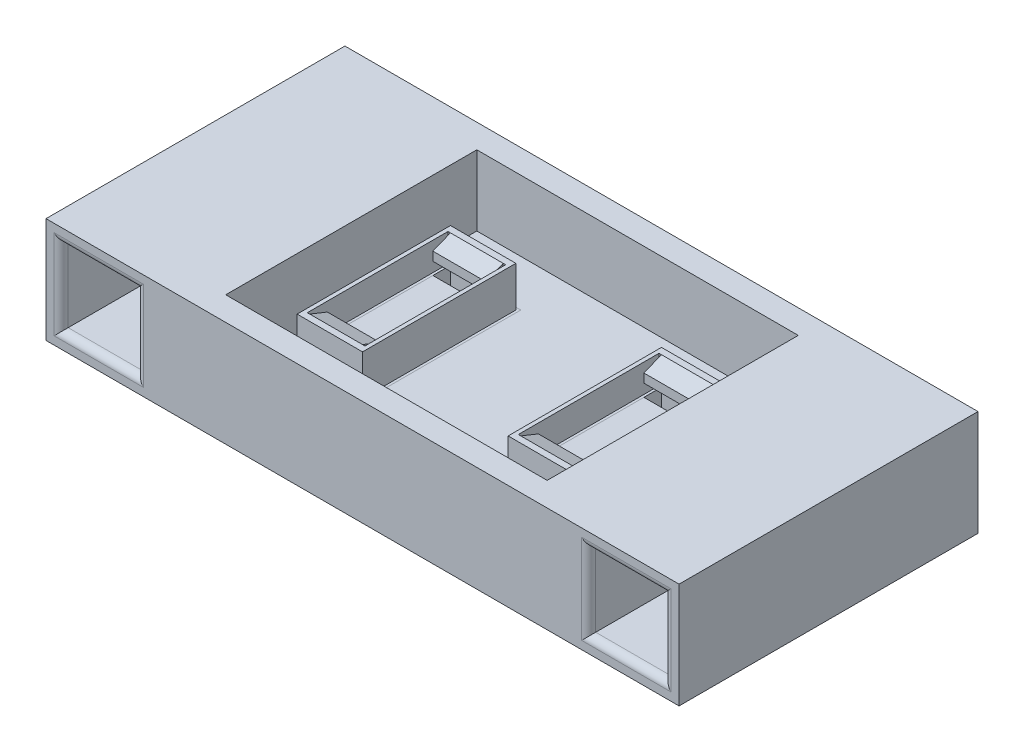
SolidWorks part; units mm, degrees
material "Custom Plastic"
ref_plane "Front Plane" through (0, 0, 0) normal (0, 0, 1) x (1, 0, 0)
ref_plane "Top Plane" through (0, 0, 0) normal (0, 1, 0) x (1, 0, 0)
ref_plane "Right Plane" through (0, 0, 0) normal (1, 0, 0) x (0, 0, -1)
sketch "Sketch1" plane through (0, 0, 0) normal (0, 1, 0) x (1, 0, 0)
  line L1 (-82.9493, 33.6982) -> (97.0507, 33.6982)
  line L2 (-82.9493, 33.6982) -> (-82.9493, -51.3018)
  line L3 (-82.9493, -51.3018) -> (97.0507, -51.3018)
  line L4 (97.0507, 33.6982) -> (97.0507, -51.3018)
  dimension "D1" = 180
  dimension "D2" = 85
extrude "Boss-Extrude1" add sketch "Sketch1" along normal blind 30
sketch "Sketch2" plane through (0, 0, 51.3018) normal (0, 0, 1) x (1, 0, 0)
  line L0 (-82.9493, 0) -> (97.0507, 0) construction
  line L1 (-77.9493, 25) -> (-57.9493, 25)
  line L2 (-77.9493, 25) -> (-77.9493, 5)
  line L3 (-77.9493, 5) -> (-57.9493, 5)
  line L4 (-57.9493, 25) -> (-57.9493, 5)
  line L5 (-77.9493, 25) -> (-57.9493, 5) construction
  line L6 (-77.9493, 5) -> (-57.9493, 25) construction
  line L7 (72.0507, 25) -> (92.0507, 25)
  line L8 (72.0507, 25) -> (72.0507, 5)
  line L9 (72.0507, 5) -> (92.0507, 5)
  line L10 (92.0507, 25) -> (92.0507, 5)
  line L11 (72.0507, 25) -> (92.0507, 5) construction
  line L12 (72.0507, 5) -> (92.0507, 25) construction
  line L13 (-82.9493, 30) -> (-82.9493, 0) construction
  line L14 (97.0507, 30) -> (97.0507, 0) construction
  point P0 (-67.9493, 15)
  point P5 (82.0507, 15)
  dimension "D1" = 15
  dimension "D2" = 20
  dimension "D3" = 20
  dimension "D4" = 15
  dimension "D5" = 20
  dimension "D6" = 20
  dimension "D7" = 15
  dimension "D8" = 15
extrude "Cut-Extrude1" cut sketch "Sketch2" against normal blind 75
sketch "Sketch3" plane through (0, 30, 0) normal (0, 1, 0) x (1, 0, 0)
  line L0 (-82.9493, 33.6982) -> (-82.9493, -51.3018) construction
  line L1 (-37.9493, 26.1982) -> (52.0507, 26.1982)
  line L2 (-37.9493, 26.1982) -> (-37.9493, -43.8018)
  line L3 (-37.9493, -43.8018) -> (52.0507, -43.8018)
  line L4 (52.0507, 26.1982) -> (52.0507, -43.8018)
  line L5 (-37.9493, 26.1982) -> (52.0507, -43.8018) construction
  line L6 (-37.9493, -43.8018) -> (52.0507, 26.1982) construction
  line L8 (-82.9493, -51.3018) -> (97.0507, -51.3018) construction
  line L9 (97.0507, -51.3018) -> (97.0507, 33.6982) construction
  point P0 (7.0507, -8.8018)
  dimension "D1" = 90
  dimension "D2" = 70
  dimension "D3" = 90
  dimension "D4" = 42.5
  dimension "D5" = 90
extrude "Cut-Extrude2" cut sketch "Sketch3" against normal blind 20
sketch "Sketch4" plane through (0, 10, 0) normal (0, 1, 0) x (1, 0, 0)
  line L0 (52.0507, 26.1982) -> (-37.9493, 26.1982) construction
  line L1 (-32.9493, 13.6982) -> (-12.9493, 13.6982)
  line L2 (-32.9493, 13.6982) -> (-32.9493, -31.3018)
  line L3 (-32.9493, -31.3018) -> (-12.9493, -31.3018)
  line L4 (-12.9493, 13.6982) -> (-12.9493, -31.3018)
  line L5 (-32.9493, 13.6982) -> (-12.9493, -31.3018) construction
  line L6 (-32.9493, -31.3018) -> (-12.9493, 13.6982) construction
  line L7 (27.0507, 13.6982) -> (47.0507, 13.6982)
  line L8 (27.0507, 13.6982) -> (27.0507, -31.3018)
  line L9 (27.0507, -31.3018) -> (47.0507, -31.3018)
  line L10 (47.0507, 13.6982) -> (47.0507, -31.3018)
  line L11 (27.0507, 13.6982) -> (47.0507, -31.3018) construction
  line L12 (27.0507, -31.3018) -> (47.0507, 13.6982) construction
  line L14 (52.0507, -43.8018) -> (52.0507, 26.1982) construction
  line L15 (-37.9493, 26.1982) -> (-37.9493, -43.8018) construction
  point P0 (-22.9493, -8.8018)
  point P5 (37.0507, -8.8018)
  dimension "D1" = 35
  dimension "D2" = 35
  dimension "D3" = 15
  dimension "D4" = 15
  dimension "D5" = 20
  dimension "D6" = 20
  dimension "D7" = 45
  dimension "D8" = 45
extrude "Boss-Extrude2" add sketch "Sketch4" along normal blind 20
sketch "Sketch5" plane through (0, 30, 0) normal (0, 1, 0) x (1, 0, 0)
  line L0 (-12.9493, -31.3018) -> (-12.9493, 13.6982) construction
  line L1 (-30.4493, 11.1982) -> (-15.4493, 11.1982)
  line L2 (-30.4493, 11.1982) -> (-30.4493, -28.8018)
  line L3 (-30.4493, -28.8018) -> (-15.4493, -28.8018)
  line L4 (-15.4493, 11.1982) -> (-15.4493, -28.8018)
  line L5 (29.5507, 11.1982) -> (44.5507, 11.1982)
  line L6 (29.5507, 11.1982) -> (29.5507, -28.8018)
  line L7 (29.5507, -28.8018) -> (44.5507, -28.8018)
  line L8 (44.5507, 11.1982) -> (44.5507, -28.8018)
  line L9 (-32.9493, 13.6982) -> (-32.9493, -31.3018) construction
  line L10 (-12.9493, 13.6982) -> (-32.9493, 13.6982) construction
  line L11 (-32.9493, -31.3018) -> (-12.9493, -31.3018) construction
  line L12 (27.0507, -31.3018) -> (47.0507, -31.3018) construction
  line L13 (27.0507, 13.6982) -> (27.0507, -31.3018) construction
  line L14 (47.0507, 13.6982) -> (27.0507, 13.6982) construction
  line L16 (47.0507, -31.3018) -> (47.0507, 13.6982) construction
  dimension "D1" = 2.5
  dimension "D2" = 2.5
  dimension "D3" = 2.5
  dimension "D4" = 2.5
  dimension "D5" = 2.5
  dimension "D6" = 2.5
  dimension "D7" = 2.5
  dimension "D8" = 2.5
extrude "Cut-Extrude3" cut sketch "Sketch5" against normal blind 15
sketch "Sketch6" plane through (47.0507, 0, 0) normal (1, 0, 0) x (0, 0, -1)
  line L0 (-51.3018, 30) -> (33.6982, 30) construction
  line L1 (-31.5859, 30) -> (20.0648, 30)
  line L2 (-31.5859, 30) -> (-31.5859, 21.4951)
  line L3 (-31.5859, 21.4951) -> (20.0648, 21.4951)
  line L4 (20.0648, 30) -> (20.0648, 21.4951)
extrude "Cut-Extrude4" cut sketch "Sketch6" against normal blind 82
sketch "Sketch7" plane through (44.5507, 0, 0) normal (-1, 0, 0) x (0, 0, 1)
  line L1 (28.8018, 21.4951) -> (-11.1982, 21.4951) construction
  line L11 (-11.1982, 21.4951) -> (-6.1982, 19.4951)
  line L12 (-6.1982, 19.4951) -> (-6.1982, 16.9951)
  line L13 (-6.1982, 16.9951) -> (-11.1982, 16.9951)
  line L14 (-11.1982, 15) -> (-11.1982, 21.4951) construction
  line L15 (-11.1982, 16.9951) -> (-11.1982, 21.4951)
  line L16 (28.8018, 21.4951) -> (28.8018, 16.9951)
  line L17 (28.8018, 15) -> (28.8018, 21.4951) construction
  line L18 (28.8018, 16.9951) -> (23.8018, 16.9951)
  line L19 (23.8018, 16.9951) -> (23.8018, 19.4951)
  line L20 (23.8018, 19.4951) -> (28.8018, 21.4951)
  dimension "D1" = 4.5
  dimension "D2" = 2
  dimension "D3" = 5
  dimension "D4" = 5
  dimension "D5" = 4.5
  dimension "D6" = 2
extrude "Boss-Extrude3" add sketch "Sketch7" along normal blind 77
sketch "Sketch10" plane through (0, 21.4951, 0) normal (0, 1, 0) x (1, 0, 0)
  line L1 (-12.9493, 11.1982) -> (27.0507, 11.1982)
  line L2 (-12.9493, 11.1982) -> (-12.9493, -28.8018)
  line L3 (-12.9493, -28.8018) -> (27.0507, -28.8018)
  line L4 (27.0507, 11.1982) -> (27.0507, -28.8018)
extrude "Cut-Extrude5" cut sketch "Sketch10" against normal blind 9
sketch "Sketch16" plane through (0, 15, 0) normal (0, 1, 0) x (1, 0, 0)
  line L1 (-30.4493, 11.1982) -> (-15.4493, 11.1982)
  line L2 (-30.4493, 11.1982) -> (-30.4493, -28.8018)
  line L3 (-30.4493, -28.8018) -> (-15.4493, -28.8018)
  line L4 (-15.4493, 11.1982) -> (-15.4493, -28.8018)
  line L5 (29.5507, 11.1982) -> (44.5507, 11.1982)
  line L6 (29.5507, 11.1982) -> (29.5507, -28.8018)
  line L7 (29.5507, -28.8018) -> (44.5507, -28.8018)
  line L8 (44.5507, 11.1982) -> (44.5507, -28.8018)
extrude "Cut-Extrude6" cut sketch "Sketch16" against normal blind 1.5
sketch "Sketch17" plane through (0, 0, 51.3018) normal (0, 0, 1) x (1, 0, 0)
  line L0 (72.0507, 25) -> (72.0507, 5) construction
  line L1 (-78.6493, 25.7) -> (-57.2493, 25.7)
  line L2 (-78.6493, 25.7) -> (-78.6493, 4.3)
  line L3 (-78.6493, 4.3) -> (-57.2493, 4.3)
  line L4 (-57.2493, 25.7) -> (-57.2493, 4.3)
  line L5 (-78.6493, 25.7) -> (-57.2493, 4.3) construction
  line L6 (-78.6493, 4.3) -> (-57.2493, 25.7) construction
  line L7 (71.3507, 25.7) -> (92.7507, 25.7)
  line L8 (71.3507, 25.7) -> (71.3507, 4.3)
  line L9 (71.3507, 4.3) -> (92.7507, 4.3)
  line L10 (92.7507, 25.7) -> (92.7507, 4.3)
  line L11 (71.3507, 25.7) -> (92.7507, 4.3) construction
  line L12 (71.3507, 4.3) -> (92.7507, 25.7) construction
  line L14 (72.0507, 5) -> (92.0507, 5) construction
  line L15 (-77.9493, 25) -> (-77.9493, 5) construction
  line L16 (-77.9493, 5) -> (-57.9493, 5) construction
  point P0 (-67.9493, 15)
  point P5 (82.0507, 15)
  dimension "D1" = 10
  dimension "D2" = 10
  dimension "D3" = 10.7
  dimension "D4" = 10.7
  dimension "D5" = 10
  dimension "D6" = 10
  dimension "D7" = 10.7
  dimension "D8" = 10.7
extrude "Cut-Extrude8" cut sketch "Sketch17" against normal blind 75
sketch "Sketch18" plane through (0, 10, 0) normal (0, 1, 0) x (1, 0, 0)
  line L0 (-37.9493, 26.1982) -> (-37.9493, -43.8018) construction
  line L1 (-38.6493, 26.8982) -> (52.7507, 26.8982)
  line L2 (-38.6493, 26.8982) -> (-38.6493, -44.5018)
  line L3 (-38.6493, -44.5018) -> (52.7507, -44.5018)
  line L4 (52.7507, 26.8982) -> (52.7507, -44.5018)
  line L5 (-38.6493, 26.8982) -> (52.7507, -44.5018) construction
  line L6 (-38.6493, -44.5018) -> (52.7507, 26.8982) construction
  line L8 (52.0507, 26.1982) -> (-37.9493, 26.1982) construction
  line L10 (-37.9493, 26.1982) -> (52.0507, 26.1982)
  line L11 (-37.9493, 26.1982) -> (-37.9493, -43.8018)
  line L12 (-37.9493, -43.8018) -> (52.0507, -43.8018)
  line L13 (52.0507, 26.1982) -> (52.0507, -43.8018)
  line L14 (-37.9493, 26.1982) -> (52.0507, -43.8018) construction
  line L15 (-37.9493, -43.8018) -> (52.0507, 26.1982) construction
  point P0 (7.0507, -8.8018)
  point P9 (7.0507, -8.8018)
  dimension "D1" = 45
  dimension "D2" = 35
  dimension "D3" = 45.7
  dimension "D4" = 35.7
extrude "Cut-Extrude10" cut sketch "Sketch18" along normal blind 50
sketch "Sketch21" plane through (0, 13.5, 0) normal (0, 1, 0) x (1, 0, 0)
  line L1 (-30.4493, 11.1982) -> (-15.4493, 11.1982)
  line L2 (-30.4493, 11.1982) -> (-30.4493, 6.1982)
  line L3 (-30.4493, 6.1982) -> (-15.4493, 6.1982)
  line L4 (-15.4493, 11.1982) -> (-15.4493, 6.1982)
  line L5 (-30.4493, -28.8018) -> (-15.4493, -28.8018)
  line L6 (-30.4493, -28.8018) -> (-30.4493, -23.8018)
  line L7 (-30.4493, -23.8018) -> (-15.4493, -23.8018)
  line L8 (-15.4493, -28.8018) -> (-15.4493, -23.8018)
  line L9 (29.5507, 11.1982) -> (44.5507, 11.1982)
  line L10 (29.5507, 11.1982) -> (29.5507, 6.1982)
  line L11 (29.5507, 6.1982) -> (44.5507, 6.1982)
  line L12 (44.5507, 11.1982) -> (44.5507, 6.1982)
  line L13 (44.5507, -23.8018) -> (29.5507, -23.8018)
  line L14 (44.5507, -23.8018) -> (44.5507, -28.8018)
  line L15 (44.5507, -28.8018) -> (29.5507, -28.8018)
  line L16 (29.5507, -23.8018) -> (29.5507, -28.8018)
extrude "Cut-Extrude15" cut sketch "Sketch21" against normal blind 30
sketch "Sketch25" plane through (0, 21.4951, 0) normal (0, 1, 0) x (1, 0, 0)
  line L1 (-30.4493, 11.1982) -> (-31.1459, 11.1982)
  line L2 (-30.4493, 11.1982) -> (-30.4493, -28.8296)
  line L3 (-30.4493, -28.8296) -> (-31.1459, -28.8296)
  line L4 (-31.1459, 11.1982) -> (-31.1459, -28.8296)
  line L5 (-15.4493, -28.8018) -> (-14.7459, -28.8018)
  line L6 (-15.4493, -28.8018) -> (-15.4493, 11.1982)
  line L7 (-15.4493, 11.1982) -> (-14.7459, 11.1982)
  line L8 (-14.7459, -28.8018) -> (-14.7459, 11.1982)
extrude "Cut-Extrude18" cut sketch "Sketch25" against normal blind 8
sketch "Sketch26" plane through (0, 21.4951, 0) normal (0, 1, 0) x (1, 0, 0)
  line L1 (29.5507, 11.1982) -> (28.8515, 11.1982)
  line L2 (29.5507, 11.1982) -> (29.5507, -28.8018)
  line L3 (29.5507, -28.8018) -> (28.8515, -28.8018)
  line L4 (28.8515, 11.1982) -> (28.8515, -28.8018)
  line L5 (44.5507, -28.8018) -> (45.2462, -28.8018)
  line L6 (44.5507, -28.8018) -> (44.5507, 11.1982)
  line L7 (44.5507, 11.1982) -> (45.2462, 11.1982)
  line L8 (45.2462, -28.8018) -> (45.2462, 11.1982)
extrude "Cut-Extrude19" cut sketch "Sketch26" against normal blind 8
sketch "Sketch27" plane through (0, 21.4951, 0) normal (0, 1, 0) x (1, 0, 0)
  line L0 (47.0507, -31.3018) -> (27.0507, -31.3018)
  line L1 (-32.9493, 13.6982) -> (-12.9493, 13.6982)
  line L2 (-32.9493, 13.6982) -> (-32.9493, -31.3018)
  line L3 (-32.9493, -31.3018) -> (-12.9493, -31.3018)
  line L4 (-12.9493, 13.6982) -> (-12.9493, -31.3018)
  line L5 (-32.2493, 12.9982) -> (-13.6493, 12.9982)
  line L6 (-32.2493, 12.9982) -> (-32.2493, -30.6018)
  line L7 (-32.2493, -30.6018) -> (-13.6493, -30.6018)
  line L8 (-13.6493, 12.9982) -> (-13.6493, -30.6018)
  line L9 (-38.6493, -44.5018) -> (52.7507, -44.5018) construction
  line L10 (-38.6493, 26.8982) -> (52.7507, 26.8982) construction
  line L11 (7.0507, -44.5018) -> (7.0507, 26.8982) construction
  line L12 (46.3507, -30.6018) -> (27.7507, -30.6018)
  line L13 (27.7507, 12.9982) -> (27.7507, -30.6018)
  line L14 (46.3507, 12.9982) -> (27.7507, 12.9982)
  line L15 (46.3507, 12.9982) -> (46.3507, -30.6018)
  line L16 (47.0507, 13.6982) -> (47.0507, -31.3018)
  line L17 (47.0507, 13.6982) -> (27.0507, 13.6982)
  line L18 (27.0507, 13.6982) -> (27.0507, -31.3018)
  dimension "D1" = 0.7
  dimension "D2" = 0.7
  dimension "D3" = 0.7
  dimension "D4" = 0.7
extrude "Cut-Extrude24" cut sketch "Sketch27" against normal blind 11.5
sketch "Sketch28" plane through (0, 0, 51.3018) normal (0, 0, 1) x (1, 0, 0)
  line L0 (-57.2493, 25.7) -> (-78.6493, 25.7) construction
  line L1 (-77.9493, 25) -> (-57.9493, 25)
  line L2 (-77.9493, 25) -> (-77.9493, 5)
  line L3 (-77.9493, 5) -> (-57.9493, 5)
  line L4 (-57.9493, 25) -> (-57.9493, 5)
  line L5 (-78.6493, 25.7) -> (-78.6493, 4.3) construction
  line L6 (-57.2493, 4.3) -> (-57.2493, 25.7) construction
  line L7 (-78.6493, 4.3) -> (-57.2493, 4.3) construction
  line L8 (-77.9493, 19.62) -> (-75.9482, 17.6189)
  line L9 (-75.9482, 17.6189) -> (-75.9482, 20.2989)
  line L10 (-75.9482, 20.2989) -> (-74.5882, 20.2989)
  line L11 (-74.5882, 20.2989) -> (-72.0426, 17.7533)
  line L12 (-72.0426, 17.7533) -> (-72.0426, 12.2467)
  line L13 (-72.0426, 12.2467) -> (-74.5882, 9.7011)
  line L14 (-74.5882, 9.7011) -> (-75.9482, 9.7011)
  line L15 (-75.9482, 9.7011) -> (-75.9482, 12.3811)
  line L16 (-75.9482, 12.3811) -> (-77.9493, 10.38)
  line L17 (-77.9493, 10.38) -> (-77.9493, 19.62)
  line L18 (-67.9493, 25) -> (-67.9493, 5) construction
  line L19 (-67.9493, 5) -> (-67.9493, 25) construction
  line L20 (-59.9504, 12.3811) -> (-57.9493, 10.38)
  line L21 (-59.9504, 9.7011) -> (-59.9504, 12.3811)
  line L22 (-61.3104, 9.7011) -> (-59.9504, 9.7011)
  line L23 (-63.856, 12.2467) -> (-61.3104, 9.7011)
  line L24 (-63.856, 17.7533) -> (-63.856, 12.2467)
  line L25 (-61.3104, 20.2989) -> (-63.856, 17.7533)
  line L26 (-59.9504, 20.2989) -> (-61.3104, 20.2989)
  line L27 (-59.9504, 17.6189) -> (-59.9504, 20.2989)
  line L28 (-57.9493, 19.62) -> (-59.9504, 17.6189)
  line L29 (-57.9493, 10.38) -> (-57.9493, 19.62)
  line L30 (7.0507, 30) -> (7.0507, 0) construction
  line L31 (-82.9493, 0) -> (97.0507, 0) construction
  line L32 (-82.9493, 30) -> (97.0507, 30) construction
  line L33 (7.0507, 0) -> (7.0507, 30) construction
  line L34 (74.0518, 9.7011) -> (74.0518, 12.3811)
  line L35 (75.4118, 9.7011) -> (74.0518, 9.7011)
  line L36 (77.9574, 12.2467) -> (75.4118, 9.7011)
  line L37 (77.9574, 17.7533) -> (77.9574, 12.2467)
  line L38 (75.4118, 20.2989) -> (77.9574, 17.7533)
  line L39 (74.0518, 20.2989) -> (75.4118, 20.2989)
  line L40 (74.0518, 17.6189) -> (74.0518, 20.2989)
  line L41 (72.0507, 19.62) -> (74.0518, 17.6189)
  line L42 (72.0507, 10.38) -> (72.0507, 19.62)
  line L43 (74.0518, 12.3811) -> (72.0507, 10.38)
  line L44 (88.6896, 9.7011) -> (90.0496, 9.7011)
  line L45 (90.0496, 9.7011) -> (90.0496, 12.3811)
  line L46 (86.144, 12.2467) -> (88.6896, 9.7011)
  line L47 (90.0496, 12.3811) -> (92.0507, 10.38)
  line L48 (90.0496, 20.2989) -> (88.6896, 20.2989)
  line L49 (92.0507, 19.62) -> (90.0496, 17.6189)
  line L50 (90.0496, 17.6189) -> (90.0496, 20.2989)
  line L51 (88.6896, 20.2989) -> (86.144, 17.7533)
  line L52 (86.144, 17.7533) -> (86.144, 12.2467)
  line L53 (92.0507, 25) -> (92.0507, 5)
  line L54 (72.0507, 25) -> (72.0507, 5)
  line L55 (92.0507, 5) -> (72.0507, 5)
  line L56 (92.0507, 25) -> (72.0507, 25)
  line L57 (92.0507, 19.62) -> (92.0507, 10.38)
  dimension "D1" = 0.7
  dimension "D2" = 0.7
  dimension "D3" = 0.7
  dimension "D4" = 0.7
  dimension "D5" = 5.38
  dimension "D6" = 5.38
  dimension "D7" = 2.83
  dimension "D8" = 2.83
  dimension "D9" = 2.68
  dimension "D10" = 2.68
  dimension "D11" = 1.36
  dimension "D12" = 1.36
  dimension "D13" = 3.6
  dimension "D14" = 3.6
extrude "Boss-Extrude7" add sketch "Sketch28" against normal blind 82 contours L43 L34 L35 L36 L37 L38 L39 L40 L41 L42 | L53 L49 L50 L48 L51 L52 L46 L44 L45 L47 | L16 L15 L14 L13 L12 L11 L10 L9 L8 L2 | L4 L28 L27 L26 L25 L24 L23 L22 L21 L20 region at (-75.0334, 15, 51.3018) region at (-60.8652, 15, 51.3018) region at (74.9666, 15, 51.3018) region at (89.1348, 15, 51.3018)
sketch "Sketch32" plane through (0, 0, 51.3018) normal (0, 0, 1) x (1, 0, 0)
  line L1 (-78.6493, 25.7) -> (-57.2493, 25.7)
  line L2 (-78.6493, 25.7) -> (-78.6493, 4.3)
  line L3 (-78.6493, 4.3) -> (-57.2493, 4.3)
  line L4 (-57.2493, 25.7) -> (-57.2493, 4.3)
  line L5 (71.3507, 25.7) -> (92.7507, 25.7)
  line L6 (71.3507, 25.7) -> (71.3507, 4.3)
  line L7 (71.3507, 4.3) -> (92.7507, 4.3)
  line L8 (92.7507, 25.7) -> (92.7507, 4.3)
extrude "Cut-Extrude26" cut sketch "Sketch32" against normal blind 65
sketch "Sketch33" plane through (0, 0, -13.6982) normal (0, 0, 1) x (1, 0, 0)
  line L1 (75.4118, 20.2989) -> (78.2892, 20.2989)
  line L2 (75.4118, 20.2989) -> (75.4118, 8.7716)
  line L3 (75.4118, 8.7716) -> (78.2892, 8.7716)
  line L4 (78.2892, 20.2989) -> (78.2892, 8.7716)
extrude "Cut-Extrude27" cut sketch "Sketch33" against normal blind 10
sketch "Sketch34" plane through (0, 0, -13.6982) normal (0, 0, 1) x (1, 0, 0)
  line L1 (88.6896, 20.2989) -> (85.4495, 20.2989)
  line L2 (88.6896, 20.2989) -> (88.6896, 8.3666)
  line L3 (88.6896, 8.3666) -> (85.4495, 8.3666)
  line L4 (85.4495, 20.2989) -> (85.4495, 8.3666)
  line L5 (-74.5882, 9.7011) -> (-70.7727, 9.7011)
  line L6 (-74.5882, 9.7011) -> (-74.5882, 21.691)
  line L7 (-74.5882, 21.691) -> (-70.7727, 21.691)
  line L8 (-70.7727, 9.7011) -> (-70.7727, 21.691)
  line L9 (-61.3104, 20.2989) -> (-66.3845, 20.2989)
  line L10 (-61.3104, 20.2989) -> (-61.3104, 8.3666)
  line L11 (-61.3104, 8.3666) -> (-66.3845, 8.3666)
  line L12 (-66.3845, 20.2989) -> (-66.3845, 8.3666)
extrude "Cut-Extrude28" cut sketch "Sketch34" against normal blind 10 contours L6 L5 L8 L7 | L10 L9 L12 L11 | L2 L1 L4 L3
sketch "Sketch35" plane through (0, 0, -13.6982) normal (0, 0, 1) x (1, 0, 0)
  line L1 (-75.9482, 17.6189) -> (-77.9493, 17.6189)
  line L2 (-75.9482, 17.6189) -> (-75.9482, 19.62)
  line L3 (-75.9482, 19.62) -> (-77.9493, 19.62)
  line L4 (-77.9493, 17.6189) -> (-77.9493, 19.62)
  line L5 (-75.9482, 12.3811) -> (-77.9493, 12.3811)
  line L6 (-75.9482, 12.3811) -> (-75.9482, 9.367)
  line L7 (-75.9482, 9.367) -> (-77.9493, 9.367)
  line L8 (-77.9493, 12.3811) -> (-77.9493, 9.367)
  line L9 (-59.9504, 17.6189) -> (-57.886, 17.6189)
  line L10 (-59.9504, 17.6189) -> (-59.9504, 20.4782)
  line L11 (-59.9504, 20.4782) -> (-57.886, 20.4782)
  line L12 (-57.886, 17.6189) -> (-57.886, 20.4782)
  line L13 (-59.9504, 12.3811) -> (-57.886, 12.3811)
  line L14 (-59.9504, 12.3811) -> (-59.9504, 8.8231)
  line L15 (-59.9504, 8.8231) -> (-57.886, 8.8231)
  line L16 (-57.886, 12.3811) -> (-57.886, 8.8231)
  line L17 (74.0518, 17.6189) -> (72.0507, 17.6189)
  line L18 (74.0518, 17.6189) -> (74.0518, 19.62)
  line L19 (74.0518, 19.62) -> (72.0507, 19.62)
  line L20 (72.0507, 17.6189) -> (72.0507, 19.62)
  line L21 (74.0518, 12.3811) -> (72.0507, 12.3811)
  line L22 (74.0518, 12.3811) -> (74.0518, 9.367)
  line L23 (74.0518, 9.367) -> (72.0507, 9.367)
  line L24 (72.0507, 12.3811) -> (72.0507, 9.367)
  line L25 (90.0496, 12.3811) -> (92.2163, 12.3811)
  line L26 (90.0496, 12.3811) -> (90.0496, 8.8231)
  line L27 (90.0496, 8.8231) -> (92.2163, 8.8231)
  line L28 (92.2163, 12.3811) -> (92.2163, 8.8231)
  line L29 (90.0496, 17.6189) -> (92.2163, 17.6189)
  line L30 (90.0496, 17.6189) -> (90.0496, 20.4782)
  line L31 (90.0496, 20.4782) -> (92.2163, 20.4782)
  line L32 (92.2163, 17.6189) -> (92.2163, 20.4782)
extrude "Cut-Extrude29" cut sketch "Sketch35" against normal blind 10
fillet "Fillet3" radius 0.25 8 edges at (74.0518, 18.9589, -13.6982) (74.7318, 20.2989, -13.6982) (75.4118, 15, -13.6982) (74.7318, 9.7011, -13.6982) (74.0518, 11.0411, -13.6982) (73.0512, 12.3811, -13.6982) (72.0507, 15, -13.6982) (73.0512, 17.6189, -13.6982)
fillet "Fillet4" radius 0.25 24 edges at (-59.9504, 11.0411, -13.6982) (-60.6304, 9.7011, -13.6982) (-61.3104, 15, -13.6982) (-60.6304, 20.2989, -13.6982) (-59.9504, 18.9589, -13.6982) (-58.9499, 17.6189, -13.6982) (-57.9493, 15, -13.6982) (-58.9499, 12.3811, -13.6982) (-77.9493, 15, -13.6982) (-76.9488, 17.6189, -13.6982) (-75.9482, 18.9589, -13.6982) (-75.2682, 20.2989, -13.6982) (-74.5882, 15, -13.6982) (-75.2682, 9.7011, -13.6982) (-75.9482, 11.0411, -13.6982) (-76.9488, 12.3811, -13.6982) (90.0496, 11.0411, -13.6982) (89.3696, 9.7011, -13.6982) (88.6896, 15, -13.6982) (89.3696, 20.2989, -13.6982) (90.0496, 18.9589, -13.6982) (91.0501, 17.6189, -13.6982) (92.0507, 15, -13.6982) (91.0501, 12.3811, -13.6982)
sketch "Sketch37" plane through (0, 0, -23.6982) normal (0, 0, 1) x (1, 0, 0)
  line L1 (-78.6493, 25.7) -> (-57.2493, 25.7)
  line L2 (-78.6493, 25.7) -> (-78.6493, 4.3)
  line L3 (-78.6493, 4.3) -> (-57.2493, 4.3)
  line L4 (-57.2493, 25.7) -> (-57.2493, 4.3)
  line L5 (-78.1493, 25.2) -> (-57.7493, 25.2)
  line L6 (-78.1493, 25.2) -> (-78.1493, 4.8)
  line L7 (-78.1493, 4.8) -> (-57.7493, 4.8)
  line L8 (-57.7493, 25.2) -> (-57.7493, 4.8)
  line L9 (-77.9493, 17.6189) -> (-78.1493, 17.6189)
  line L10 (-77.9493, 17.6189) -> (-77.9493, 12.3811)
  line L11 (-77.9493, 12.3811) -> (-78.1493, 12.3811)
  line L12 (-78.1493, 17.6189) -> (-78.1493, 12.3811)
  line L13 (-57.9493, 17.6189) -> (-57.7493, 17.6189)
  line L14 (-57.9493, 17.6189) -> (-57.9493, 12.3811)
  line L15 (-57.9493, 12.3811) -> (-57.7493, 12.3811)
  line L16 (-57.7493, 17.6189) -> (-57.7493, 12.3811)
  line M18 (-57.9493, 17.6189) -> (-57.9493, 12.3811)
  line M25 (-57.2493, 4.3) -> (-57.2493, 25.7)
  line M26 (-57.2493, 25.7) -> (-78.6493, 25.7)
  line M27 (-78.6493, 25.7) -> (-78.6493, 4.3)
  line M28 (-78.6493, 4.3) -> (-57.2493, 4.3)
  dimension "D1" = 0.5
  dimension "D2" = 0.5
  dimension "D3" = 0.5
  dimension "D4" = 0.5
extrude "Boss-Extrude9" add sketch "Sketch37" along normal blind 10 contours L5 L8 L7 L6 M28 M25 M26 M27 | L15 L8 L13 M18 | L10 L11 L12 L9 region at (-67.9493, 25.3974, -23.6982) region at (-57.8493, 15, -23.6982)
sketch "Sketch38" plane through (0, 0, -23.6982) normal (0, 0, 1) x (1, 0, 0)
  line L1 (71.3507, 25.7) -> (92.7507, 25.7)
  line L2 (71.3507, 25.7) -> (71.3507, 4.3)
  line L3 (71.3507, 4.3) -> (92.7507, 4.3)
  line L4 (92.7507, 25.7) -> (92.7507, 4.3)
  line L5 (71.8507, 4.8) -> (92.2507, 4.8)
  line L6 (71.8507, 4.8) -> (71.8507, 25.2)
  line L7 (71.8507, 25.2) -> (92.2507, 25.2)
  line L8 (92.2507, 4.8) -> (92.2507, 25.2)
  line L9 (72.0507, 12.3811) -> (71.8507, 12.3811)
  line L10 (72.0507, 12.3811) -> (72.0507, 17.5981)
  line L11 (72.0507, 17.5981) -> (71.8507, 17.5981)
  line L12 (71.8507, 12.3811) -> (71.8507, 17.5981)
  line L13 (92.0507, 17.6189) -> (92.2507, 17.6189)
  line L14 (92.0507, 17.6189) -> (92.0507, 12.3811)
  line L15 (92.0507, 12.3811) -> (92.2507, 12.3811)
  line L16 (92.2507, 17.6189) -> (92.2507, 12.3811)
  line M16 (72.0507, 12.3811) -> (72.0507, 17.6189)
  line M18 (92.0507, 17.6189) -> (92.0507, 12.3811)
  line M25 (92.7507, 4.3) -> (92.7507, 25.7)
  line M26 (92.7507, 25.7) -> (71.3507, 25.7)
  line M27 (71.3507, 25.7) -> (71.3507, 4.3)
  line M28 (71.3507, 4.3) -> (92.7507, 4.3)
  dimension "D1" = 0.5
  dimension "D2" = 0.5
  dimension "D3" = 0.5
  dimension "D4" = 0.5
extrude "Boss-Extrude10" add sketch "Sketch38" along normal blind 10 contours L8 L5 L6 L7 M28 M25 M26 M27 | L11 L6 L9 M16 | L15 L8 L13 M18 region at (82.0507, 25.3974, -23.6982) region at (71.9507, 14.9896, -23.6982) region at (92.1507, 15, -23.6982)
fillet "Fillet7" radius 0.25 32 edges at (71.3507, 15, -13.6982) (82.0507, 25.7, -13.6982) (92.7507, 15, -13.6982) (82.0507, 4.3, -13.6982) (92.1507, 12.3811, -13.6982) (92.0507, 15, -13.6982) (92.1507, 17.6189, -13.6982) (92.2507, 8.5906, -13.6982) (82.0507, 25.2, -13.6982) (71.8507, 8.5906, -13.6982) (71.9507, 17.5981, -13.6982) (72.0507, 14.9896, -13.6982) (71.9507, 12.3811, -13.6982) (71.8507, 21.399, -13.6982) (82.0507, 4.8, -13.6982) (92.2507, 21.4094, -13.6982) (-78.1493, 21.4094, -13.6982) (-78.0493, 17.6189, -13.6982) (-77.9493, 15, -13.6982) (-78.0493, 12.3811, -13.6982) (-78.1493, 8.5906, -13.6982) (-67.9493, 4.8, -13.6982) (-57.7493, 21.4094, -13.6982) (-57.8493, 12.3811, -13.6982) (-57.9493, 15, -13.6982) (-57.8493, 17.6189, -13.6982) (-57.7493, 8.5906, -13.6982) (-67.9493, 25.2, -13.6982) (-78.6493, 15, -13.6982) (-67.9493, 25.7, -13.6982) (-57.2493, 15, -13.6982) (-67.9493, 4.3, -13.6982)
fillet "Fillet8" radius 2 8 edges at (-67.9493, 4.3, 51.3018) (-67.9493, 25.7, 51.3018) (-57.2493, 15, 51.3018) (-78.6493, 15, 51.3018) (92.7507, 15, 51.3018) (82.0507, 4.3, 51.3018) (71.3507, 15, 51.3018) (82.0507, 25.7, 51.3018)
